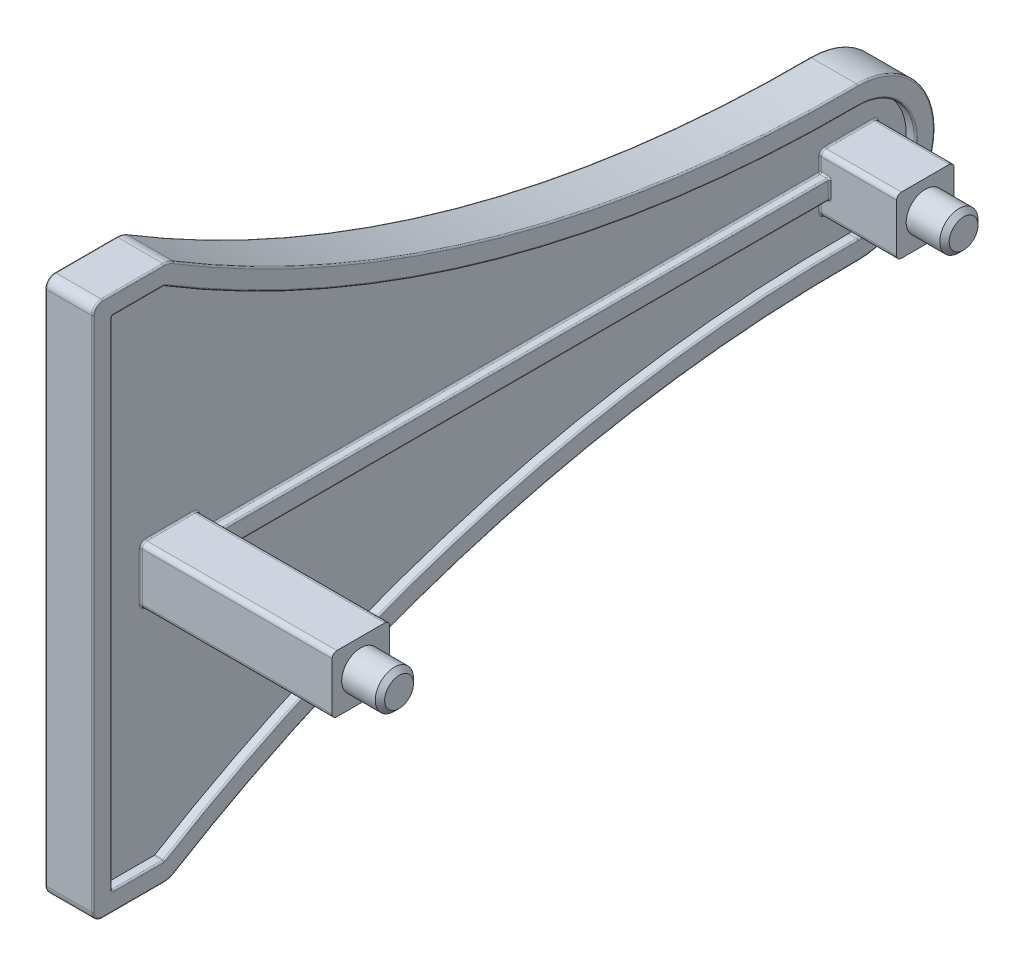
SolidWorks part; units mm, degrees
material "1060 Alloy"
ref_plane "Front" through (0, 0, 0) normal (0, 0, 1) x (1, 0, 0)
ref_plane "Top" through (0, 0, 0) normal (0, 1, 0) x (1, 0, 0)
ref_plane "Right" through (0, 0, 0) normal (1, 0, 0) x (0, 0, -1)
sketch "Sketch1" plane through (0, 0, 0) normal (1, 0, 0) x (0, 0, -1)
  line L0 (0, 0) -> (279.4, 0) construction
  line L3 (0, -85.725) -> (0, 85.725)
  line L4 (3.175, 88.9) -> (23.618, 88.9)
  line L5 (3.175, -88.9) -> (23.618, -88.9)
  arc A4 (253.8234, -25.3994) -> (253.8234, 25.3994) centre (254, 0) ccw
  arc A5 (26.9108, 87.9795) -> (253.8234, 25.3994) centre (250.8207, 457.1889) ccw
  arc A6 (0, 85.725) -> (3.175, 88.9) centre (3.175, 85.725) cw
  arc A7 (23.618, 88.9) -> (26.9108, 87.9795) centre (23.618, 82.55) cw
  arc A8 (26.9108, -87.9795) -> (253.8234, -25.3994) centre (250.8207, -457.1889) cw
  arc A9 (23.618, -88.9) -> (26.9108, -87.9795) centre (23.618, -82.55) ccw
  arc A10 (0, -85.725) -> (3.175, -88.9) centre (3.175, -85.725) ccw
  point P1 (25.4, -88.9)
  point P11 (0, 88.9)
  point P15 (25.4, 88.9)
  point P25 (0, 0)
  point P26 (0, -88.9)
  dimension "D1" = 25.4
  dimension "D2" = 88.9
  dimension "D5" = 431.8
  dimension "D3" = 50.8
  dimension "D6" = 3.175
  dimension "D7" = 6.35
  dimension "D4" = 254
extrude "Boss-Extrude1" add sketch "Sketch1" along normal blind 12.7
sketch "Sketch2" plane through (12.7, 0, 0) normal (1, 0, 0) x (0, 0, -1)
  line L0 (-1000, 0) -> (49000, 0) construction
  line L1 (0, 85.725) -> (0, -85.725) construction
  line L2 (20.6248, 9.525) -> (36.5252, 9.525)
  line L3 (19.05, 7.9502) -> (19.05, -7.9502)
  line L4 (20.6248, -9.525) -> (36.5252, -9.525)
  line L5 (38.1, 7.9502) -> (38.1, -7.9502)
  line L6 (19.05, 9.525) -> (38.1, -9.525) construction
  line L7 (19.05, -9.525) -> (38.1, 9.525) construction
  arc A0 (20.6248, 9.525) -> (19.05, 7.9502) centre (20.6248, 7.9502) ccw
  arc A1 (36.5252, 9.525) -> (38.1, 7.9502) centre (36.5252, 7.9502) cw
  arc A2 (36.5252, -9.525) -> (38.1, -7.9502) centre (36.5252, -7.9502) ccw
  arc A3 (19.05, -7.9502) -> (20.6248, -9.525) centre (20.6248, -7.9502) ccw
  point P1 (28.575, 0)
  dimension "D4" = 1.5748
  dimension "D1" = 19.05
  dimension "D2" = 19.05
  dimension "D3" = 19.05
extrude "Boss-Extrude2" add sketch "Sketch2" along normal blind 63.5
sketch "Sketch3" plane through (12.7, 0, 0) normal (1, 0, 0) x (0, 0, -1)
  line L0 (-1000, 0) -> (49000, 0) construction
  line L1 (0, 85.725) -> (0, -85.725) construction
  line L7 (261.9502, 9.525) -> (246.0498, 9.525)
  line L8 (263.525, 7.9502) -> (263.525, -7.9502)
  line L9 (261.9502, -9.525) -> (246.0498, -9.525)
  line L10 (244.475, 7.9502) -> (244.475, -7.9502)
  line L11 (263.525, 9.525) -> (244.475, -9.525) construction
  line L12 (263.525, -9.525) -> (244.475, 9.525) construction
  arc A0 (263.525, -7.9502) -> (261.9502, -9.525) centre (261.9502, -7.9502) cw
  arc A1 (246.0498, -9.525) -> (244.475, -7.9502) centre (246.0498, -7.9502) cw
  arc A2 (246.0498, 9.525) -> (244.475, 7.9502) centre (246.0498, 7.9502) ccw
  arc A3 (261.9502, 9.525) -> (263.525, 7.9502) centre (261.9502, 7.9502) cw
  point P1 (254, 0)
  point P5 (0, 0)
  dimension "D3" = 1.5748
  dimension "D1" = 19.05
  dimension "D2" = 19.05
extrude "Boss-Extrude3" add sketch "Sketch3" along normal blind 25.4
sketch "Sketch4" plane through (76.2, 0, 0) normal (1, 0, 0) x (0, 0, -1)
  line L2 (28.575, 0) -> (49000, 0) construction
  line L3 (0, 85.725) -> (0, -85.725) construction
  line L4 (28.575, -990.475) -> (28.575, 0) construction
  line L5 (36.5252, 9.525) -> (20.6248, 9.525) construction
  circle A0 centre (28.575, 0) radius 6.35
  point P5 (0, 0)
  point P10 (28.575, 9.525)
  dimension "D1" = 12.7
extrude "Boss-Extrude4" add sketch "Sketch4" along normal blind 12.7
sketch "Sketch5" plane through (38.1, 0, 0) normal (1, 0, 0) x (0, 0, -1)
  circle A0 centre (254, 0) radius 6.35
  dimension "D1" = 12.7
extrude "Boss-Extrude5" add sketch "Sketch5" along normal blind 12.7
chamfer "Chamfer1" distance 1.5748 angle 45 2 edges at (50.8, 0, -260.35) (88.9, 0, -34.925)
sketch "Sketch6" plane through (12.7, 0, 0) normal (1, 0, 0) x (0, 0, -1)
  line L0 (6.35, -82.55) -> (23.618, -82.55)
  line L1 (6.35, 82.55) -> (6.35, -82.55)
  line L2 (23.618, 82.55) -> (6.35, 82.55)
  line L3 (23.618, 88.9) -> (3.175, 88.9)
  line L4 (0, 85.725) -> (0, -85.725)
  line L5 (3.175, -88.9) -> (23.618, -88.9)
  line L6 (23.618, 88.9) -> (3.175, 88.9)
  line L7 (0, 85.725) -> (0, -85.725)
  line L8 (3.175, -88.9) -> (23.618, -88.9)
  arc A0 (253.8675, -19.0495) -> (23.618, -82.55) centre (250.8207, -457.1889) ccw
  arc A1 (23.618, -82.55) -> (23.618, -82.55) centre (23.618, -82.55) ccw
  arc A2 (6.35, -82.55) -> (6.35, -82.55) centre (6.35, -82.55) ccw
  arc A3 (6.35, 82.55) -> (6.35, 82.55) centre (6.35, 82.55) ccw
  arc A4 (23.618, 82.55) -> (23.618, 82.55) centre (23.618, 82.55) ccw
  arc A5 (23.618, 82.55) -> (253.8675, 19.0495) centre (250.8207, 457.1889) ccw
  arc A6 (253.8675, -19.0495) -> (253.8675, 19.0495) centre (254, 0) ccw
  arc A7 (26.9108, 87.9795) -> (253.8234, 25.3994) centre (250.8207, 457.1889) ccw
  arc A8 (26.9108, 87.9795) -> (23.618, 88.9) centre (23.618, 82.55) ccw
  arc A9 (3.175, 88.9) -> (0, 85.725) centre (3.175, 85.725) ccw
  arc A10 (0, -85.725) -> (3.175, -88.9) centre (3.175, -85.725) ccw
  arc A11 (23.618, -88.9) -> (26.9108, -87.9795) centre (23.618, -82.55) ccw
  arc A12 (253.8234, -25.3994) -> (26.9108, -87.9795) centre (250.8207, -457.1889) ccw
  arc A13 (253.8234, -25.3994) -> (253.8234, 25.3994) centre (254, 0) ccw
  arc A14 (26.9108, 87.9795) -> (253.8234, 25.3994) centre (250.8207, 457.1889) ccw
  arc A15 (26.9108, 87.9795) -> (23.618, 88.9) centre (23.618, 82.55) ccw
  arc A16 (3.175, 88.9) -> (0, 85.725) centre (3.175, 85.725) ccw
  arc A17 (0, -85.725) -> (3.175, -88.9) centre (3.175, -85.725) ccw
  arc A18 (23.618, -88.9) -> (26.9108, -87.9795) centre (23.618, -82.55) ccw
  arc A19 (253.8234, -25.3994) -> (26.9108, -87.9795) centre (250.8207, -457.1889) ccw
  arc A20 (253.8234, -25.3994) -> (253.8234, 25.3994) centre (254, 0) ccw
  dimension "D1" = 0
  dimension "D2" = 6.35
extrude "Boss-Extrude6" add sketch "Sketch6" along normal blind 3.175
sketch "Sketch7" plane through (12.7, 0, 0) normal (1, 0, 0) x (0, 0, -1)
  line L0 (38.1, 3.175) -> (38.1, -3.175)
  line L1 (38.1, 3.175) -> (244.475, 3.175)
  line L2 (38.1, -7.9502) -> (38.1, 7.9502) construction
  line L3 (244.475, 7.9502) -> (244.475, -7.9502) construction
  line L4 (244.475, 3.175) -> (244.475, -3.175)
  line L5 (244.475, -3.175) -> (38.1, -3.175)
  line L6 (38.1, -7.9502) -> (38.1, 7.9502) construction
  point P0 (38.1, 0)
  dimension "D1" = 6.35
extrude "Boss-Extrude8" add sketch "Sketch7" along normal up to surface (3.175 mm away) up to face at (15.875, 0, -63.0749)
fillet "Fillet1" radius 0.508 34 edges at (15.875, 34.8077, -134.3323) (15.875, 0, -273.05) (15.875, -40.9292, -136.0205) (15.875, -88.6656, -25.3275) (15.875, -88.9, -13.3965) (15.875, -87.9701, -0.9299) (15.875, 0, 0) (15.875, 87.9701, -0.9299) (15.875, 88.9, -13.3965) (15.875, 88.6656, -25.3275) (15.875, 40.9292, -136.0205) (0, -88.6656, -25.3275) (0, -88.9, -13.3965) (0, -87.9701, -0.9299) (0, 0, 0) (0, 87.9701, -0.9299) (0, 88.9, -13.3965) (0, 88.6656, -25.3275) (0, 40.9292, -136.0205) (0, 0, -279.4) (15.875, 3.175, -141.2875) (15.875, -3.175, -141.2875) (15.875, -34.8077, -134.3323) (15.875, 0, -279.4) (0, -40.9292, -136.0205) (15.875, 82.55, -14.984) (15.875, 0, -6.35) (15.875, -82.55, -14.984) (12.7, 3.175, -141.2875) (12.7, -3.175, -141.2875) (14.2875, 82.55, -6.35) (14.2875, -82.55, -6.35) (14.2875, -82.55, -23.618) (14.2875, 82.55, -23.618)
fillet "Fillet2" radius 0.508 32 edges at (12.7, -9.0638, -19.5112) (12.7, 0, -19.05) (12.7, 9.0638, -19.5112) (12.7, 9.525, -28.575) (12.7, 9.0638, -37.6388) (12.7, 5.8166, -38.1) (12.8488, 3.3238, -38.1) (14.2875, 3.175, -38.1) (15.7262, 3.0262, -38.1) (15.875, 0, -38.1) (15.7262, -3.0262, -38.1) (14.2875, -3.175, -38.1) (12.8488, -3.3238, -38.1) (12.7, -5.8166, -38.1) (12.7, -9.0638, -37.6388) (12.7, -9.0638, -244.9362) (12.7, -5.8166, -244.475) (12.8488, -3.3238, -244.475) (14.2875, -3.175, -244.475) (15.7262, -3.0262, -244.475) (15.875, 0, -244.475) (15.7262, 3.0262, -244.475) (14.2875, 3.175, -244.475) (12.8488, 3.3238, -244.475) (12.7, 5.8166, -244.475) (12.7, 9.0638, -244.9362) (12.7, 9.525, -254) (12.7, 9.0638, -263.0638) (12.7, 0, -263.525) (12.7, -9.0638, -263.0638) (12.7, -9.525, -28.575) (12.7, -9.525, -254)
